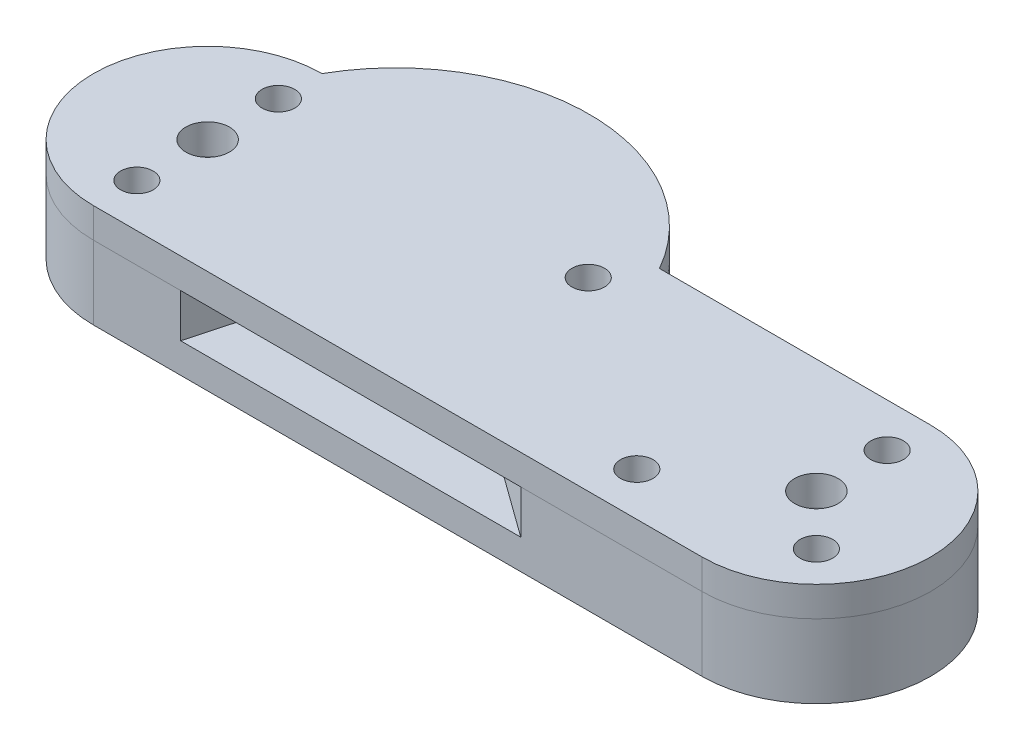
SolidWorks part; units mm, degrees
ref_plane "Front Plane" through (0, 0, 0) normal (0, 0, 1) x (1, 0, 0)
ref_plane "Top Plane" through (0, 0, 0) normal (0, 1, 0) x (1, 0, 0)
ref_plane "Right Plane" through (0, 0, 0) normal (1, 0, 0) x (0, 0, -1)
sketch "Sketch1" plane through (0, 0, 0) normal (0, 1, 0) x (1, 0, 0)
  line L0 (0, -10.5004) -> (-55.9305, -10.5004)
  line L1 (0, 10.5004) -> (-55.9305, 10.5004)
  line L5 (0, 11.5004) -> (-55.9305, 11.5004) construction
  line L6 (0, -11.5004) -> (-55.9305, -11.5004) construction
  circle A0 centre (0, 0) radius 2
  arc A1 (0, -10.5004) -> (0, 10.5004) centre (0, 0) ccw
  arc A2 (-55.9305, 10.5004) -> (-55.9305, -10.5004) centre (-55.9305, 0) ccw
  circle A3 centre (-55.9305, 0) radius 2
  arc A7 (0, -11.5004) -> (0, 11.5004) centre (0, 0) ccw construction
  arc A8 (-55.9305, 11.5004) -> (-55.9305, -11.5004) centre (-55.9305, 0) ccw construction
  arc A9 (-67.2423, -5.04) -> (-54.9145, -15.6487) centre (-55.7741, -4.1805) ccw construction
  arc A10 (-55.9305, 10.5004) -> (-55.9305, -10.5004) centre (-55.9305, 0) ccw construction
  circle A11 centre (0, 0) radius 67.4309 construction
  arc A12 (-59.8966, 30.973) -> (-67.2423, -5.04) centre (0, 0) ccw construction
  dimension "D1" = 4
  dimension "D2" = 1
  dimension "D3" = 4
extrude "Boss-Extrude1" add sketch "Sketch1" along normal mid plane 9.5
sketch "Sketch3" plane through (0, 0, 0) normal (0, 1, 0) x (1, 0, 0)
  line L0 (0, 0) -> (-47.1525, -15.3208) construction
  line L1 (0, 0) -> (24.7895, -42.9367) construction
  line L2 (0, 0) -> (-55.9305, 0) construction
  line L3 (24.7895, -42.9367) -> (-41.5934, 5.0595) construction
  line L4 (-41.5934, 5.0595) -> (-47.1525, -15.3208) construction
  line L5 (-41.5934, 5.0595) -> (-37.6461, 19.5308) construction
  line L6 (-41.5934, 5.0595) -> (-53.749, 13.8482) construction
  line L7 (22.8477, -44.0007) -> (-38.0092, 0) construction
  line L8 (-35.7518, 18.8753) -> (-39.2995, 5.869)
  line L9 (-43.8873, 4.25) -> (-54.8123, 12.149)
  line L11 (26.6452, -41.8104) -> (-39.2995, 5.869)
  line L12 (-39.6108, 19.9279) -> (-42.7627, 8.3729) construction
  line L13 (-42.7627, 8.3729) -> (-52.4686, 15.3905) construction
  line L14 (-40.9004, 0) -> (-45.9674, -18.5763) construction
  line L15 (-43.8873, 4.25) -> (-48.2065, -11.585)
  line L18 (-40.4216, 6.6802) -> (-50.8477, 14.2185) construction
  line L20 (-41.5934, 5.0595) -> (-52.0196, 12.5978) construction
  line L21 (-42.7652, 3.4387) -> (-53.1914, 10.977) construction
  line L23 (-43.5229, 5.5858) -> (-49.082, -14.7945) construction
  line L26 (-39.6639, 4.5332) -> (-45.223, -15.8471) construction
  line L27 (25.9613, -41.316) -> (-40.4216, 6.6802) construction
  line L28 (23.6177, -44.5574) -> (-42.7652, 3.4387) construction
  arc A1 (-48.2065, -11.585) -> (26.6452, -41.8104) centre (0, 0) ccw
  arc A4 (-55.9305, 10.5004) -> (-55.9305, -10.5004) centre (-55.9305, 0) ccw construction
  arc A7 (-35.7518, 18.8753) -> (-54.8123, 12.149) centre (-41.5934, 5.0595) ccw
  dimension "D1" = 99.1581
  dimension "D3" = 120
  dimension "D6" = 30
  dimension "D2" = 18
  dimension "D4" = 2
  dimension "D5" = 2
extrude "Cut-Extrude1" cut sketch "Sketch3" against normal mid plane 4
sketch "Sketch5" plane through (0, 0, 0) normal (0, 1, 0) x (1, 0, 0)
  line L0 (-40.4241, 1.7461) -> (-52.5322, 10.5004) construction
  line L1 (-40.4241, 1.7461) -> (-35.7382, 18.9254) construction
  line L2 (-52.5322, 10.5004) -> (-43.8873, 4.25) construction
  line L3 (-39.2995, 5.869) -> (-38.0362, 10.5004) construction
  line L4 (-55.9305, 10.5004) -> (-24.9177, 10.5004)
  line L5 (0, 10.5004) -> (-55.9305, 10.5004) construction
  circle A0 centre (-40.4241, 1.7461) radius 17.807
extrude "Boss-Extrude2" add sketch "Sketch5" along normal up to surface and the other way up to surface contours A0 region at (-40.4241, 0, -14.2141) up to face at (0, 4.75, 2) other way up to face at (-27.9653, -4.75, 0)
sketch "Sketch6" plane through (0, 0, 0) normal (0, 1, 0) x (1, 0, 0)
  line L0 (-39.2995, 5.869) -> (-16.6593, -10.5004)
  line L1 (-47.9107, -10.5004) -> (-43.8873, 4.25)
  line L2 (-43.8873, 4.25) -> (-54.8544, 12.1794)
  line L3 (-39.2995, 5.869) -> (-35.7382, 18.9254)
  line L4 (-16.6593, -10.5004) -> (-39.2995, 5.869) construction
  line L5 (-43.8873, 4.25) -> (-47.9107, -10.5004) construction
  line L6 (-52.5322, 10.5004) -> (-43.8873, 4.25) construction
  line L7 (-39.2995, 5.869) -> (-38.0362, 10.5004) construction
  line L8 (-55.9305, -10.5004) -> (0, -10.5004) construction
  line L9 (-16.6593, -10.5004) -> (-47.9107, -10.5004)
  arc A0 (-24.9177, 10.5004) -> (-55.9305, 10.5004) centre (-40.4241, 1.7461) ccw construction
  arc A1 (-35.7382, 18.9254) -> (-54.8544, 12.1794) centre (-40.4241, 1.7461) ccw
extrude "Cut-Extrude2" cut sketch "Sketch6" against normal mid plane 4
sketch "Sketch7" plane through (0, -4.75, 0) normal (0, -1, 0) x (1, 0, 0)
  line L0 (0, 0) -> (4.5965, 4.5965) construction
  line L1 (0, 0) -> (6.5004, 0) construction
  line L4 (0, 6.5004) -> (-55.9305, 6.5004)
  line L5 (-27.4616, -6.5004) -> (0, -6.5004)
  line L6 (0, 6.5004) -> (-55.9305, 6.5004) construction
  line L7 (-55.9305, -6.5004) -> (0, -6.5004) construction
  circle A3 centre (-27.4616, -6.5004) radius 1.5
  circle A4 centre (0, -6.5004) radius 1.5
  circle A5 centre (4.5965, 4.5965) radius 1.5
  arc A6 (0, -6.5004) -> (0, 6.5004) centre (0, 0) ccw
  arc A7 (-55.9305, 6.5004) -> (-53.5442, -6.0466) centre (-55.9305, 0) ccw
  arc A8 (-53.5442, -6.0466) -> (-27.4616, -6.5004) centre (-40.4241, -1.7461) ccw
  arc A9 (0, -6.5004) -> (0, 6.5004) centre (0, 0) ccw construction
  arc A10 (-55.9305, 6.5004) -> (-53.5442, -6.0466) centre (-55.9305, 0) ccw construction
  arc A11 (-53.5442, -6.0466) -> (-27.4616, -6.5004) centre (-40.4241, -1.7461) ccw construction
  circle A12 centre (-10, 6.5004) radius 1.5
  circle A13 centre (-55.9305, 6.5004) radius 1.5
  circle A14 centre (-55.9305, -6.5004) radius 1.5
  dimension "D4" = 3
  dimension "D2" = 10
  dimension "D3" = 45
  dimension "D1" = 4
extrude "Cut-Extrude3" cut sketch "Sketch7" against normal through all
sketch "Sketch8" plane through (0, -4.75, 0) normal (0, -1, 0) x (1, 0, 0)
  circle A0 centre (-55.9305, 6.5004) radius 2.75
  circle A1 centre (-55.9305, -6.5004) radius 2.75
  circle A2 centre (-27.4616, -6.5004) radius 2.75
  circle A3 centre (-10, 6.5004) radius 2.75
  circle A4 centre (4.5965, 4.5965) radius 2.75
  circle A5 centre (0, -6.5004) radius 2.75
  dimension "D1" = 5.5
extrude "Cut-Extrude4" cut sketch "Sketch8" against normal blind 3.2
ref_plane "Plane1" through (0, 2, 0) normal (0, -1, 0) x (-1, 0, 0)
split "Split1" trim tools "Plane1" bodies to split 110 resulting bodies 111 112
